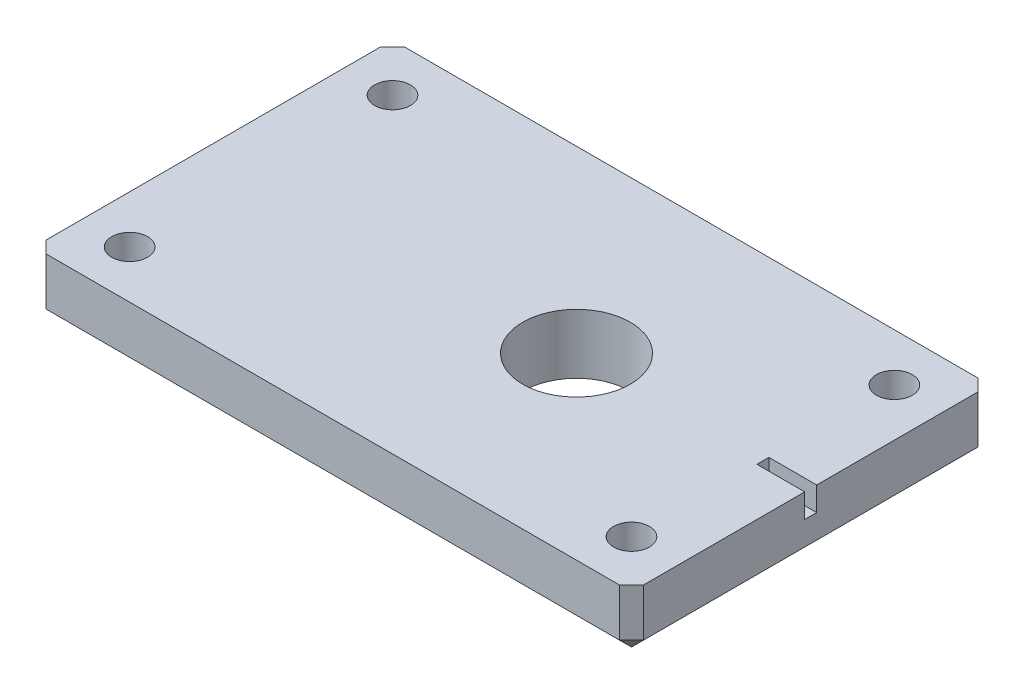
SolidWorks part; units mm, degrees
ref_plane "Front" through (0, 0, 0) normal (0, 0, 1) x (1, 0, 0)
ref_plane "Top" through (0, 0, 0) normal (0, 1, 0) x (1, 0, 0)
ref_plane "Right" through (0, 0, 0) normal (1, 0, 0) x (0, 0, -1)
sketch "Sketch1" plane through (0, 0, 0) normal (0, 1, 0) x (1, 0, 0)
  line L1 (-25, 15) -> (25, 15)
  line L2 (-25, 15) -> (-25, -15)
  line L3 (-25, -15) -> (25, -15)
  line L4 (25, 15) -> (25, -15)
  line L5 (-25, 15) -> (25, -15) construction
  line L6 (-25, -15) -> (25, 15) construction
  point P0 (0, 0)
  dimension "D1" = 30
  dimension "D2" = 50
extrude "Boss-Extrude1" add sketch "Sketch1" along normal blind 5
ref_plane "Plane1" through (0, 5, 0) normal (0, 1, 0) x (1, 0, 0)
sketch "Sketch2" plane through (0, 5, 0) normal (0, 1, 0) x (1, 0, 0)
  line L0 (-50, 0) -> (50, 0) construction
  line L1 (21, 0.5) -> (25, 0.5)
  line L2 (21, 0.5) -> (21, -0.5)
  line L3 (21, -0.5) -> (25, -0.5)
  line L4 (25, 0.5) -> (25, -0.5)
  line L5 (21, 0.5) -> (25, -0.5) construction
  line L6 (21, -0.5) -> (25, 0.5) construction
  line L7 (25, -15) -> (25, 15) construction
  point P0 (23, 0)
  dimension "D1" = 1
  dimension "D2" = 4
extrude "Cut-Extrude1" cut sketch "Sketch2" against normal blind 2
sketch "Sketch3" plane through (0, 5, 0) normal (0, 1, 0) x (1, 0, 0)
  line L0 (-50, 0) -> (50, 0) construction
  line L1 (25, 0.5) -> (25, 15) construction
  line L2 (-12.23, 11) -> (13.0032, 11) construction
  line L3 (-11.8064, 0) -> (9.9776, 0) construction
  line L4 (25, 15) -> (-25, 15) construction
  line L5 (-25, 15) -> (-25, -15) construction
  line L6 (0, 17.8125) -> (0, 7.1626) construction
  line L7 (0, -50) -> (0, 50) construction
  circle A0 centre (5.4, 0) radius 4.5
  circle A1 centre (-21, 11) radius 1.5
  circle A2 centre (21, 11) radius 1.5
  circle A3 centre (21, -11) radius 1.5
  circle A4 centre (-21, -11) radius 1.5
  dimension "D1" = 9
  dimension "D3" = 3
  dimension "D2" = 19.6
  dimension "D4" = 4
  dimension "D5" = 4
extrude "Cut-Extrude2" cut sketch "Sketch3" against normal blind 22 contours A0
extrude "Cut-Extrude3" cut sketch "Sketch3<3>" against normal blind 22
sketch "Sketch3<3>" plane through (0, 5, 0) normal (0, 1, 0) x (1, 0, 0) same geometry as "Sketch3"
chamfer "Chamfer1" distance 1 angle 45 8 edges at (-25, 2.5, -15) (-25, 2.5, 15) (25, 2.5, 15) (25, 2.5, -15) (-25, 0, 0) (0, 0, 15) (25, 0, 0) (0, 0, -15)
